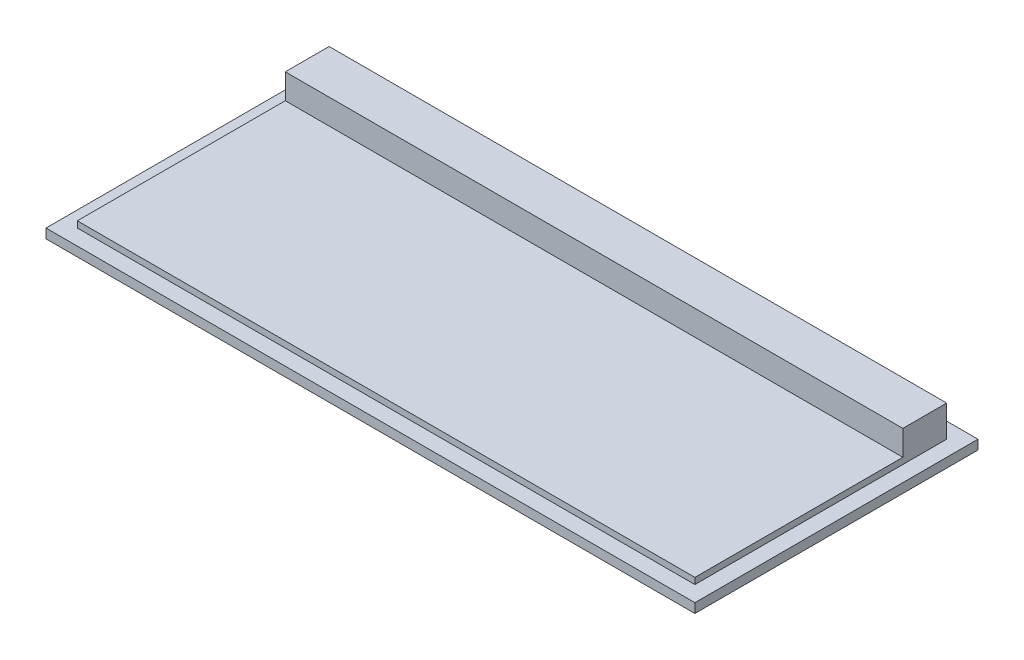
SolidWorks part; units mm, degrees
ref_plane "Front Plane" through (0, 0, 0) normal (0, 0, 1) x (1, 0, 0)
ref_plane "Top Plane" through (0, 0, 0) normal (0, 1, 0) x (1, 0, 0)
ref_plane "Right Plane" through (0, 0, 0) normal (1, 0, 0) x (0, 0, -1)
sketch "Sketch1" plane through (0, 0, 0) normal (1, 0, 0) x (0, 0, -1)
  line L0 (0, 0) -> (114.808, 0)
  line L28 (0, 0) -> (0, 3.81)
  line L29 (0, 3.81) -> (114.808, 3.81)
  line L30 (114.808, 0) -> (114.808, 3.81)
  dimension "D1" = 114.808
  dimension "D2" = 3.81
extrude "Boss-Extrude1" add sketch "Sketch1" along normal blind 263.144
sketch "Sketch2" plane through (0, 3.81, 0) normal (0, 1, 0) x (1, 0, 0)
  line L8 (6.35, 108.458) -> (6.35, 6.35)
  line L9 (6.35, 6.35) -> (256.794, 6.35)
  line L10 (256.794, 6.35) -> (256.794, 108.458)
  line L11 (256.794, 108.458) -> (6.35, 108.458)
  line L12 (6.35, 108.458) -> (6.35, 6.35)
  line L13 (6.35, 6.35) -> (256.794, 6.35)
  line L14 (256.794, 6.35) -> (256.794, 108.458)
  line L15 (256.794, 108.458) -> (6.35, 108.458)
  dimension "D1" = 6.35
extrude "Boss-Extrude2" add sketch "Sketch2" along normal blind 2.54
sketch "Sketch3" plane through (6.35, 0, 0) normal (-1, 0, 0) x (0, 0, 1)
  line L1 (-108.458, 6.35) -> (-90.678, 6.35)
  line L2 (-108.458, 6.35) -> (-108.458, 16.51)
  line L3 (-108.458, 16.51) -> (-90.678, 16.51)
  line L4 (-90.678, 6.35) -> (-90.678, 16.51)
  dimension "D1" = 10.16
  dimension "D2" = 17.78
extrude "Boss-Extrude3" add sketch "Sketch3" against normal blind 250.444
sketch "Sketch4" plane through (6.35, 0, 0) normal (-1, 0, 0) x (0, 0, 1)
  line L0 (-93.98, 7.112) -> (-93.98, 9.3148)
  line L2 (-105.156, 9.3148) -> (-105.156, 7.112)
  line L3 (-93.98, 7.112) -> (-105.156, 7.112)
  line L4 (-105.156, 9.3148) -> (-93.98, 9.3148)
  line L5 (-105.156, 13.208) -> (-105.156, 6.35) construction
  line L6 (-93.98, 6.35) -> (-93.98, 13.208) construction
  line L7 (-93.218, 6.35) -> (-105.918, 6.35)
  line L8 (-93.218, 7.112) -> (-105.918, 7.112) construction
  line L10 (-93.218, 6.35) -> (-93.218, 13.97)
  line L11 (-105.918, 13.97) -> (-105.918, 3.81)
  line L12 (-93.218, 13.97) -> (-105.918, 13.97)
  line L13 (-93.218, 6.35) -> (-93.218, 13.97)
  line L14 (-105.918, 13.97) -> (-105.918, 6.35)
  line L15 (-93.218, 13.97) -> (-105.918, 13.97)
  line L16 (-93.98, 13.208) -> (-105.156, 13.208) construction
  dimension "D4" = 2.2028
  dimension "D1" = 2.54
  dimension "D2" = 0.762
  dimension "D3" = 0.762
extrude "Cut-Extrude2" cut sketch "Sketch4" against normal blind 12.7
sketch "Sketch6" plane through (0, 9.3148, 0) normal (0, 1, 0) x (1, 0, 0)
  line L0 (7.8674, 100.4556) -> (7.8674, 99.0333)
  line L1 (7.8674, 103.2496) -> (17.4486, 103.2496)
  line L2 (7.8674, 103.2496) -> (7.8674, 101.8273)
  line L3 (7.8674, 101.8273) -> (17.4486, 101.8273)
  line L4 (17.4486, 103.2496) -> (17.4486, 101.8273)
  line L5 (7.8674, 100.4556) -> (17.4486, 100.4556)
  line L6 (17.4486, 100.4556) -> (17.4486, 99.0333)
  line L7 (7.8674, 99.0333) -> (17.4486, 99.0333)
  line L8 (7.8674, 97.6616) -> (7.8674, 96.2393)
  line L9 (7.8674, 97.6616) -> (17.4486, 97.6616)
  line L10 (17.4486, 97.6616) -> (17.4486, 96.2393)
  line L11 (7.8674, 96.2393) -> (17.4486, 96.2393)
  dimension "D1" = 9.5812
  dimension "D2" = 1.4222
  dimension "D3" = 101.8273
  dimension "D4" = 7.8674
  dimension "D5" = 3
extrude "Boss-Extrude4" add sketch "Sketch6" along normal blind 0.254
sketch "Sketch7" plane through (0, 0, 0) normal (0, -1, 0) x (1, 0, 0)
  line L72 (28.2706, -104.3102) -> (28.2706, -109.0361)
  line L88 (11.7606, -103.0402) -> (23.5018, -103.0402)
  line L114 (29.5406, -103.0402) -> (41.2818, -103.0402)
  line L115 (10.4906, -104.3102) -> (10.4906, -109.0361)
  line L116 (42.5518, -104.3102) -> (42.5518, -109.0361)
  line L117 (11.7606, -110.3061) -> (23.5018, -110.3061)
  line L118 (24.7718, -104.3102) -> (24.7718, -109.0361)
  line L119 (29.5406, -110.3061) -> (41.2818, -110.3061)
  line L120 (46.0506, -104.3102) -> (46.0506, -109.0361)
  line L121 (47.3206, -103.0402) -> (59.0618, -103.0402)
  line L122 (60.3318, -104.3102) -> (60.3318, -109.0361)
  line L123 (47.3206, -110.3061) -> (59.0618, -110.3061)
  line L124 (63.8306, -104.3102) -> (63.8306, -109.0361)
  line L125 (65.1006, -103.0402) -> (76.8418, -103.0402)
  line L126 (78.1118, -104.3102) -> (78.1118, -109.0361)
  line L127 (65.1006, -110.3061) -> (76.8418, -110.3061)
  line L128 (81.6106, -104.3102) -> (81.6106, -109.0361)
  line L129 (82.8806, -103.0402) -> (94.6218, -103.0402)
  line L130 (95.8918, -104.3102) -> (95.8918, -109.0361)
  line L131 (82.8806, -110.3061) -> (94.6218, -110.3061)
  line L132 (99.3906, -104.3102) -> (99.3906, -109.0361)
  line L133 (100.6606, -103.0402) -> (112.4018, -103.0402)
  line L134 (113.6718, -104.3102) -> (113.6718, -109.0361)
  line L135 (100.6606, -110.3061) -> (112.4018, -110.3061)
  line L136 (117.1706, -104.3102) -> (117.1706, -109.0361)
  line L137 (118.4406, -103.0402) -> (130.1818, -103.0402)
  line L138 (131.4518, -104.3102) -> (131.4518, -109.0361)
  line L139 (118.4406, -110.3061) -> (130.1818, -110.3061)
  line L140 (134.9506, -104.3102) -> (134.9506, -109.0361)
  line L141 (136.2206, -103.0402) -> (147.9618, -103.0402)
  line L142 (149.2318, -104.3102) -> (149.2318, -109.0361)
  line L143 (136.2206, -110.3061) -> (147.9618, -110.3061)
  line L144 (152.7306, -104.3102) -> (152.7306, -109.0361)
  line L145 (154.0006, -103.0402) -> (165.7418, -103.0402)
  line L146 (167.0118, -104.3102) -> (167.0118, -109.0361)
  line L147 (154.0006, -110.3061) -> (165.7418, -110.3061)
  line L148 (170.5106, -104.3102) -> (170.5106, -109.0361)
  line L149 (171.7806, -103.0402) -> (183.5218, -103.0402)
  line L150 (184.7918, -104.3102) -> (184.7918, -109.0361)
  line L151 (171.7806, -110.3061) -> (183.5218, -110.3061)
  line L152 (188.2906, -104.3102) -> (188.2906, -109.0361)
  line L153 (189.5606, -103.0402) -> (201.3018, -103.0402)
  line L154 (202.5718, -104.3102) -> (202.5718, -109.0361)
  line L155 (189.5606, -110.3061) -> (201.3018, -110.3061)
  line L156 (206.0706, -104.3102) -> (206.0706, -109.0361)
  line L157 (207.3406, -103.0402) -> (219.0818, -103.0402)
  line L158 (220.3518, -104.3102) -> (220.3518, -109.0361)
  line L159 (207.3406, -110.3061) -> (219.0818, -110.3061)
  line L160 (223.8506, -104.3102) -> (223.8506, -109.0361)
  line L161 (225.1206, -103.0402) -> (236.8618, -103.0402)
  line L162 (238.1318, -104.3102) -> (238.1318, -109.0361)
  line L163 (225.1206, -110.3061) -> (236.8618, -110.3061)
  line L164 (241.6306, -104.3102) -> (241.6306, -109.0361)
  line L165 (242.9006, -103.0402) -> (254.6418, -103.0402)
  line L166 (255.9118, -104.3102) -> (255.9118, -109.0361)
  line L167 (242.9006, -110.3061) -> (254.6418, -110.3061)
  line L168 (28.2086, -98.0792) -> (28.2086, -88.1833)
  line L169 (11.7606, -99.3492) -> (23.5018, -99.3492)
  line L170 (10.4906, -98.0792) -> (10.4906, -88.1833)
  line L171 (11.7606, -86.9133) -> (23.5018, -86.9133)
  line L172 (24.7718, -98.0792) -> (24.7718, -88.1833)
  line L173 (29.4786, -99.3492) -> (41.2197, -99.3492)
  line L174 (42.4897, -98.0792) -> (42.4897, -88.1833)
  line L175 (29.4786, -86.9133) -> (41.2197, -86.9133)
  line L176 (45.9265, -98.0792) -> (45.9265, -88.1833)
  line L177 (47.1965, -99.3492) -> (58.9376, -99.3492)
  line L178 (60.2076, -98.0792) -> (60.2076, -88.1833)
  line L179 (47.1965, -86.9133) -> (58.9376, -86.9133)
  line L180 (63.6444, -98.0792) -> (63.6444, -88.1833)
  line L181 (64.9144, -99.3492) -> (76.6555, -99.3492)
  line L182 (77.9255, -98.0792) -> (77.9255, -88.1833)
  line L183 (64.9144, -86.9133) -> (76.6555, -86.9133)
  line L184 (81.3623, -98.0792) -> (81.3623, -88.1833)
  line L185 (82.6323, -99.3492) -> (94.3734, -99.3492)
  line L186 (95.6434, -98.0792) -> (95.6434, -88.1833)
  line L187 (82.6323, -86.9133) -> (94.3734, -86.9133)
  line L188 (99.0802, -98.0792) -> (99.0802, -88.1833)
  line L189 (100.3502, -99.3492) -> (112.0914, -99.3492)
  line L190 (113.3614, -98.0792) -> (113.3614, -88.1833)
  line L191 (100.3502, -86.9133) -> (112.0914, -86.9133)
  line L192 (116.7981, -98.0792) -> (116.7981, -88.1833)
  line L193 (118.0681, -99.3492) -> (129.8093, -99.3492)
  line L194 (131.0793, -98.0792) -> (131.0793, -88.1833)
  line L195 (118.0681, -86.9133) -> (129.8093, -86.9133)
  line L196 (134.516, -98.0792) -> (134.516, -88.1833)
  line L197 (135.786, -99.3492) -> (147.5272, -99.3492)
  line L198 (148.7972, -98.0792) -> (148.7972, -88.1833)
  line L199 (135.786, -86.9133) -> (147.5272, -86.9133)
  line L200 (152.2339, -98.0792) -> (152.2339, -88.1833)
  line L201 (153.5039, -99.3492) -> (165.2451, -99.3492)
  line L202 (166.5151, -98.0792) -> (166.5151, -88.1833)
  line L203 (153.5039, -86.9133) -> (165.2451, -86.9133)
  line L204 (169.9519, -98.0792) -> (169.9519, -88.1833)
  line L205 (171.2219, -99.3492) -> (182.963, -99.3492)
  line L206 (184.233, -98.0792) -> (184.233, -88.1833)
  line L207 (171.2219, -86.9133) -> (182.963, -86.9133)
  line L208 (187.6698, -98.0792) -> (187.6698, -88.1833)
  line L209 (188.9398, -99.3492) -> (200.6809, -99.3492)
  line L210 (201.9509, -98.0792) -> (201.9509, -88.1833)
  line L211 (188.9398, -86.9133) -> (200.6809, -86.9133)
  line L212 (205.3877, -98.0792) -> (205.3877, -88.1833)
  line L213 (206.6577, -99.3492) -> (218.3988, -99.3492)
  line L214 (219.6688, -98.0792) -> (219.6688, -88.1833)
  line L215 (206.6577, -86.9133) -> (218.3988, -86.9133)
  line L216 (223.1056, -98.0792) -> (223.1056, -88.1833)
  line L217 (224.3756, -99.3492) -> (236.1167, -99.3492)
  line L218 (237.3867, -98.0792) -> (237.3867, -88.1833)
  line L219 (224.3756, -86.9133) -> (236.1167, -86.9133)
  line L220 (240.8235, -98.0792) -> (240.8235, -88.1833)
  line L221 (242.0935, -99.3492) -> (253.8347, -99.3492)
  line L222 (255.1047, -98.0792) -> (255.1047, -88.1833)
  line L223 (242.0935, -86.9133) -> (253.8347, -86.9133)
  line L224 (28.2086, -82.8392) -> (28.2086, -72.9433)
  line L225 (29.4786, -84.1092) -> (41.2197, -84.1092)
  line L226 (42.4897, -82.8392) -> (42.4897, -72.9433)
  line L227 (29.4786, -71.6733) -> (41.2197, -71.6733)
  line L228 (45.9265, -82.8392) -> (45.9265, -72.9433)
  line L229 (47.1965, -84.1092) -> (58.9376, -84.1092)
  line L230 (60.2076, -82.8392) -> (60.2076, -72.9433)
  line L231 (47.1965, -71.6733) -> (58.9376, -71.6733)
  line L232 (63.6444, -82.8392) -> (63.6444, -72.9433)
  line L233 (64.9144, -84.1092) -> (76.6555, -84.1092)
  line L234 (77.9255, -82.8392) -> (77.9255, -72.9433)
  line L235 (64.9144, -71.6733) -> (76.6555, -71.6733)
  line L236 (81.3623, -82.8392) -> (81.3623, -72.9433)
  line L237 (82.6323, -84.1092) -> (94.3734, -84.1092)
  line L238 (95.6434, -82.8392) -> (95.6434, -72.9433)
  line L239 (82.6323, -71.6733) -> (94.3734, -71.6733)
  line L240 (99.0802, -82.8392) -> (99.0802, -72.9433)
  line L241 (100.3502, -84.1092) -> (112.0914, -84.1092)
  line L242 (113.3614, -82.8392) -> (113.3614, -72.9433)
  line L243 (100.3502, -71.6733) -> (112.0914, -71.6733)
  line L244 (116.7981, -82.8392) -> (116.7981, -72.9433)
  line L245 (118.0681, -84.1092) -> (129.8093, -84.1092)
  line L246 (131.0793, -82.8392) -> (131.0793, -72.9433)
  line L247 (118.0681, -71.6733) -> (129.8093, -71.6733)
  line L248 (134.516, -82.8392) -> (134.516, -72.9433)
  line L249 (135.786, -84.1092) -> (147.5272, -84.1092)
  line L250 (148.7972, -82.8392) -> (148.7972, -72.9433)
  line L251 (135.786, -71.6733) -> (147.5272, -71.6733)
  line L252 (152.2339, -82.8392) -> (152.2339, -72.9433)
  line L253 (153.5039, -84.1092) -> (165.2451, -84.1092)
  line L254 (166.5151, -82.8392) -> (166.5151, -72.9433)
  line L255 (153.5039, -71.6733) -> (165.2451, -71.6733)
  line L256 (169.9519, -82.8392) -> (169.9519, -72.9433)
  line L257 (171.2219, -84.1092) -> (182.963, -84.1092)
  line L258 (184.233, -82.8392) -> (184.233, -72.9433)
  line L259 (171.2219, -71.6733) -> (182.963, -71.6733)
  line L260 (187.6698, -82.8392) -> (187.6698, -72.9433)
  line L261 (188.9398, -84.1092) -> (200.6809, -84.1092)
  line L262 (201.9509, -82.8392) -> (201.9509, -72.9433)
  line L263 (188.9398, -71.6733) -> (200.6809, -71.6733)
  line L264 (205.3877, -82.8392) -> (205.3877, -72.9433)
  line L265 (206.6577, -84.1092) -> (218.3988, -84.1092)
  line L266 (219.6688, -82.8392) -> (219.6688, -72.9433)
  line L267 (206.6577, -71.6733) -> (218.3988, -71.6733)
  line L268 (223.1056, -82.8392) -> (223.1056, -72.9433)
  line L269 (224.3756, -84.1092) -> (236.1167, -84.1092)
  line L270 (237.3867, -82.8392) -> (237.3867, -72.9433)
  line L271 (224.3756, -71.6733) -> (236.1167, -71.6733)
  line L272 (240.8235, -82.8392) -> (240.8235, -72.9433)
  line L273 (242.0935, -84.1092) -> (253.8347, -84.1092)
  line L274 (255.1047, -82.8392) -> (255.1047, -72.9433)
  line L275 (242.0935, -71.6733) -> (253.8347, -71.6733)
  line L276 (28.2086, -67.5992) -> (28.2086, -57.7033)
  line L277 (29.4786, -68.8692) -> (41.2197, -68.8692)
  line L278 (42.4897, -67.5992) -> (42.4897, -57.7033)
  line L279 (29.4786, -56.4333) -> (41.2197, -56.4333)
  line L280 (45.9265, -67.5992) -> (45.9265, -57.7033)
  line L281 (47.1965, -68.8692) -> (58.9376, -68.8692)
  line L282 (60.2076, -67.5992) -> (60.2076, -57.7033)
  line L283 (47.1965, -56.4333) -> (58.9376, -56.4333)
  line L284 (63.6444, -67.5992) -> (63.6444, -57.7033)
  line L285 (64.9144, -68.8692) -> (76.6555, -68.8692)
  line L286 (77.9255, -67.5992) -> (77.9255, -57.7033)
  line L287 (64.9144, -56.4333) -> (76.6555, -56.4333)
  line L288 (81.3623, -67.5992) -> (81.3623, -57.7033)
  line L289 (82.6323, -68.8692) -> (94.3734, -68.8692)
  line L290 (95.6434, -67.5992) -> (95.6434, -57.7033)
  line L291 (82.6323, -56.4333) -> (94.3734, -56.4333)
  line L292 (99.0802, -67.5992) -> (99.0802, -57.7033)
  line L293 (100.3502, -68.8692) -> (112.0914, -68.8692)
  line L294 (113.3614, -67.5992) -> (113.3614, -57.7033)
  line L295 (100.3502, -56.4333) -> (112.0914, -56.4333)
  line L296 (116.7981, -67.5992) -> (116.7981, -57.7033)
  line L297 (118.0681, -68.8692) -> (129.8093, -68.8692)
  line L298 (131.0793, -67.5992) -> (131.0793, -57.7033)
  line L299 (118.0681, -56.4333) -> (129.8093, -56.4333)
  line L300 (134.516, -67.5992) -> (134.516, -57.7033)
  line L301 (135.786, -68.8692) -> (147.5272, -68.8692)
  line L302 (148.7972, -67.5992) -> (148.7972, -57.7033)
  line L303 (135.786, -56.4333) -> (147.5272, -56.4333)
  line L304 (152.2339, -67.5992) -> (152.2339, -57.7033)
  line L305 (153.5039, -68.8692) -> (165.2451, -68.8692)
  line L306 (166.5151, -67.5992) -> (166.5151, -57.7033)
  line L307 (153.5039, -56.4333) -> (165.2451, -56.4333)
  line L308 (169.9519, -67.5992) -> (169.9519, -57.7033)
  line L309 (171.2219, -68.8692) -> (182.963, -68.8692)
  line L310 (184.233, -67.5992) -> (184.233, -57.7033)
  line L311 (171.2219, -56.4333) -> (182.963, -56.4333)
  line L312 (187.6698, -67.5992) -> (187.6698, -57.7033)
  line L313 (188.9398, -68.8692) -> (200.6809, -68.8692)
  line L314 (201.9509, -67.5992) -> (201.9509, -57.7033)
  line L315 (188.9398, -56.4333) -> (200.6809, -56.4333)
  line L316 (205.3877, -67.5992) -> (205.3877, -57.7033)
  line L317 (206.6577, -68.8692) -> (218.3988, -68.8692)
  line L318 (219.6688, -67.5992) -> (219.6688, -57.7033)
  line L319 (206.6577, -56.4333) -> (218.3988, -56.4333)
  line L320 (223.1056, -67.5992) -> (223.1056, -57.7033)
  line L321 (224.3756, -68.8692) -> (236.1167, -68.8692)
  line L322 (237.3867, -67.5992) -> (237.3867, -57.7033)
  line L323 (224.3756, -56.4333) -> (236.1167, -56.4333)
  line L324 (240.8235, -67.5992) -> (240.8235, -57.7033)
  line L325 (242.0935, -68.8692) -> (253.8347, -68.8692)
  line L326 (255.1047, -67.5992) -> (255.1047, -57.7033)
  line L327 (242.0935, -56.4333) -> (253.8347, -56.4333)
  line L328 (28.2086, -52.3592) -> (28.2086, -42.4633)
  line L329 (29.4786, -53.6292) -> (41.2197, -53.6292)
  line L330 (42.4897, -52.3592) -> (42.4897, -42.4633)
  line L331 (29.4786, -41.1933) -> (41.2197, -41.1933)
  line L332 (45.9265, -52.3592) -> (45.9265, -42.4633)
  line L333 (47.1965, -53.6292) -> (58.9376, -53.6292)
  line L334 (60.2076, -52.3592) -> (60.2076, -42.4633)
  line L335 (47.1965, -41.1933) -> (58.9376, -41.1933)
  line L336 (63.6444, -52.3592) -> (63.6444, -42.4633)
  line L337 (64.9144, -53.6292) -> (76.6555, -53.6292)
  line L338 (77.9255, -52.3592) -> (77.9255, -42.4633)
  line L339 (64.9144, -41.1933) -> (76.6555, -41.1933)
  line L340 (81.3623, -52.3592) -> (81.3623, -42.4633)
  line L341 (82.6323, -53.6292) -> (94.3734, -53.6292)
  line L342 (95.6434, -52.3592) -> (95.6434, -42.4633)
  line L343 (82.6323, -41.1933) -> (94.3734, -41.1933)
  line L344 (99.0802, -52.3592) -> (99.0802, -42.4633)
  line L345 (100.3502, -53.6292) -> (112.0914, -53.6292)
  line L346 (113.3614, -52.3592) -> (113.3614, -42.4633)
  line L347 (100.3502, -41.1933) -> (112.0914, -41.1933)
  line L348 (116.7981, -52.3592) -> (116.7981, -42.4633)
  line L349 (118.0681, -53.6292) -> (129.8093, -53.6292)
  line L350 (131.0793, -52.3592) -> (131.0793, -42.4633)
  line L351 (118.0681, -41.1933) -> (129.8093, -41.1933)
  line L352 (134.516, -52.3592) -> (134.516, -42.4633)
  line L353 (135.786, -53.6292) -> (147.5272, -53.6292)
  line L354 (148.7972, -52.3592) -> (148.7972, -42.4633)
  line L355 (135.786, -41.1933) -> (147.5272, -41.1933)
  line L356 (152.2339, -52.3592) -> (152.2339, -42.4633)
  line L357 (153.5039, -53.6292) -> (165.2451, -53.6292)
  line L358 (166.5151, -52.3592) -> (166.5151, -42.4633)
  line L359 (153.5039, -41.1933) -> (165.2451, -41.1933)
  line L360 (169.9519, -52.3592) -> (169.9519, -42.4633)
  line L361 (171.2219, -53.6292) -> (182.963, -53.6292)
  line L362 (184.233, -52.3592) -> (184.233, -42.4633)
  line L363 (171.2219, -41.1933) -> (182.963, -41.1933)
  line L364 (187.6698, -52.3592) -> (187.6698, -42.4633)
  line L365 (188.9398, -53.6292) -> (200.6809, -53.6292)
  line L366 (201.9509, -52.3592) -> (201.9509, -42.4633)
  line L367 (188.9398, -41.1933) -> (200.6809, -41.1933)
  line L368 (205.3877, -52.3592) -> (205.3877, -42.4633)
  line L369 (206.6577, -53.6292) -> (218.3988, -53.6292)
  line L370 (219.6688, -52.3592) -> (219.6688, -42.4633)
  line L371 (206.6577, -41.1933) -> (218.3988, -41.1933)
  line L372 (223.1056, -52.3592) -> (223.1056, -42.4633)
  line L373 (224.3756, -53.6292) -> (236.1167, -53.6292)
  line L374 (237.3867, -52.3592) -> (237.3867, -42.4633)
  line L375 (224.3756, -41.1933) -> (236.1167, -41.1933)
  line L376 (240.8235, -52.3592) -> (240.8235, -42.4633)
  line L377 (242.0935, -53.6292) -> (253.8347, -53.6292)
  line L378 (255.1047, -52.3592) -> (255.1047, -42.4633)
  line L379 (242.0935, -41.1933) -> (253.8347, -41.1933)
  line L380 (28.2086, -37.1192) -> (28.2086, -27.2233)
  line L381 (29.4786, -38.3892) -> (41.2197, -38.3892)
  line L382 (42.4897, -37.1192) -> (42.4897, -27.2233)
  line L383 (29.4786, -25.9533) -> (41.2197, -25.9533)
  line L384 (45.9265, -37.1192) -> (45.9265, -27.2233)
  line L385 (47.1965, -38.3892) -> (58.9376, -38.3892)
  line L386 (60.2076, -37.1192) -> (60.2076, -27.2233)
  line L387 (47.1965, -25.9533) -> (58.9376, -25.9533)
  line L388 (63.6444, -37.1192) -> (63.6444, -27.2233)
  line L389 (64.9144, -38.3892) -> (76.6555, -38.3892)
  line L390 (77.9255, -37.1192) -> (77.9255, -27.2233)
  line L391 (64.9144, -25.9533) -> (76.6555, -25.9533)
  line L392 (81.3623, -37.1192) -> (81.3623, -27.2233)
  line L393 (82.6323, -38.3892) -> (94.3734, -38.3892)
  line L394 (95.6434, -37.1192) -> (95.6434, -27.2233)
  line L395 (82.6323, -25.9533) -> (94.3734, -25.9533)
  line L396 (99.0802, -37.1192) -> (99.0802, -27.2233)
  line L397 (100.3502, -38.3892) -> (112.0914, -38.3892)
  line L398 (113.3614, -37.1192) -> (113.3614, -27.2233)
  line L399 (100.3502, -25.9533) -> (112.0914, -25.9533)
  line L400 (116.7981, -37.1192) -> (116.7981, -27.2233)
  line L401 (118.0681, -38.3892) -> (129.8093, -38.3892)
  line L402 (131.0793, -37.1192) -> (131.0793, -27.2233)
  line L403 (118.0681, -25.9533) -> (129.8093, -25.9533)
  line L404 (134.516, -37.1192) -> (134.516, -27.2233)
  line L405 (135.786, -38.3892) -> (147.5272, -38.3892)
  line L406 (148.7972, -37.1192) -> (148.7972, -27.2233)
  line L407 (135.786, -25.9533) -> (147.5272, -25.9533)
  line L408 (152.2339, -37.1192) -> (152.2339, -27.2233)
  line L409 (153.5039, -38.3892) -> (165.2451, -38.3892)
  line L410 (166.5151, -37.1192) -> (166.5151, -27.2233)
  line L411 (153.5039, -25.9533) -> (165.2451, -25.9533)
  line L412 (169.9519, -37.1192) -> (169.9519, -27.2233)
  line L413 (171.2219, -38.3892) -> (182.963, -38.3892)
  line L414 (184.233, -37.1192) -> (184.233, -27.2233)
  line L415 (171.2219, -25.9533) -> (182.963, -25.9533)
  line L416 (187.6698, -37.1192) -> (187.6698, -27.2233)
  line L417 (188.9398, -38.3892) -> (200.6809, -38.3892)
  line L418 (201.9509, -37.1192) -> (201.9509, -27.2233)
  line L419 (188.9398, -25.9533) -> (200.6809, -25.9533)
  line L420 (205.3877, -37.1192) -> (205.3877, -27.2233)
  line L421 (206.6577, -38.3892) -> (218.3988, -38.3892)
  line L422 (219.6688, -37.1192) -> (219.6688, -27.2233)
  line L423 (206.6577, -25.9533) -> (218.3988, -25.9533)
  line L424 (223.1056, -37.1192) -> (223.1056, -27.2233)
  line L425 (224.3756, -38.3892) -> (236.1167, -38.3892)
  line L426 (237.3867, -37.1192) -> (237.3867, -27.2233)
  line L427 (224.3756, -25.9533) -> (236.1167, -25.9533)
  line L428 (240.8235, -37.1192) -> (240.8235, -27.2233)
  line L429 (242.0935, -38.3892) -> (253.8347, -38.3892)
  line L430 (255.1047, -37.1192) -> (255.1047, -27.2233)
  line L431 (242.0935, -25.9533) -> (253.8347, -25.9533)
  line L432 (10.4906, -82.8392) -> (10.4906, -72.9433)
  line L433 (11.7606, -84.1092) -> (23.5018, -84.1092)
  line L434 (24.7718, -82.8392) -> (24.7718, -72.9433)
  line L435 (11.7606, -71.6733) -> (23.5018, -71.6733)
  line L436 (10.4906, -67.5992) -> (10.4906, -57.7033)
  line L437 (11.7606, -68.8692) -> (23.5018, -68.8692)
  line L438 (24.7718, -67.5992) -> (24.7718, -57.7033)
  line L439 (11.7606, -56.4333) -> (23.5018, -56.4333)
  line L440 (10.4906, -52.3592) -> (10.4906, -42.4633)
  line L441 (11.7606, -53.6292) -> (23.5018, -53.6292)
  line L442 (24.7718, -52.3592) -> (24.7718, -42.4633)
  line L443 (11.7606, -41.1933) -> (23.5018, -41.1933)
  line L444 (10.4906, -37.1192) -> (10.4906, -27.2233)
  line L445 (11.7606, -38.3892) -> (23.5018, -38.3892)
  line L446 (24.7718, -37.1192) -> (24.7718, -27.2233)
  line L447 (11.7606, -25.9533) -> (23.5018, -25.9533)
  line L456 (63.3401, -22.3062) -> (63.3401, -11.9933)
  line L457 (64.6101, -10.7233) -> (75.9343, -10.7233)
  line L458 (77.5445, -22.5142) -> (77.7011, -11.7854)
  line L459 (64.1931, -23.1593) -> (75.9343, -23.1593)
  line L460 (81.1201, -22.3062) -> (81.1201, -11.9933)
  line L461 (82.3901, -10.7233) -> (93.7143, -10.7233)
  line L462 (95.4013, -22.3062) -> (95.4013, -11.5764)
  line L463 (81.9731, -23.1593) -> (93.7143, -23.1593)
  line L464 (77.6228, -17.1498) -> (63.3401, -17.1498) construction
  line L465 (188.1526, -21.3738) -> (188.1526, -11.4778)
  line L466 (100.1019, -22.6438) -> (182.963, -22.6438)
  line L467 (98.8319, -21.3738) -> (98.8319, -11.4778)
  line L468 (100.1019, -10.2078) -> (182.963, -10.2078)
  line L469 (184.233, -21.3738) -> (184.233, -11.4778)
  line L470 (189.4226, -22.6438) -> (201.1637, -22.6438)
  line L471 (202.4337, -21.3738) -> (202.4337, -11.4778)
  line L472 (189.4226, -10.2078) -> (201.1637, -10.2078)
  line L473 (205.9326, -21.3738) -> (205.9326, -11.4778)
  line L474 (207.2026, -10.2078) -> (218.9437, -10.2078)
  line L475 (220.2137, -21.3738) -> (220.2137, -11.4778)
  line L476 (207.2026, -22.6438) -> (218.9437, -22.6438)
  line L477 (223.7126, -21.3738) -> (223.7126, -11.4778)
  line L478 (224.9826, -10.2078) -> (236.7237, -10.2078)
  line L479 (237.9937, -21.3738) -> (237.9937, -11.4778)
  line L480 (224.9826, -22.6438) -> (236.7237, -22.6438)
  line L481 (241.4926, -21.3738) -> (241.4926, -11.4778)
  line L482 (242.7626, -10.2078) -> (254.5037, -10.2078)
  line L483 (255.7737, -21.3738) -> (255.7737, -11.4778)
  line L484 (242.7626, -22.6438) -> (254.5037, -22.6438)
  line L486 (58.9322, -10.7233) -> (47.1911, -10.7233)
  line L487 (60.2022, -11.9933) -> (60.2022, -15.8798)
  line L488 (58.9322, -17.1498) -> (47.1911, -17.1498)
  line L489 (45.9211, -11.9933) -> (45.9211, -15.8798)
  line L490 (41.7025, -10.7534) -> (29.9613, -10.7534)
  line L491 (42.9725, -12.0234) -> (42.9725, -15.9098)
  line L492 (41.7025, -17.1798) -> (29.9613, -17.1798)
  line L493 (28.6913, -12.0234) -> (28.6913, -15.9098)
  line L494 (23.6426, -10.6966) -> (11.9015, -10.6966)
  line L495 (24.9126, -11.9666) -> (24.9126, -15.853)
  line L496 (23.6426, -17.123) -> (11.9015, -17.123)
  line L497 (10.6315, -11.9666) -> (10.6315, -15.853)
  line L498 (41.7025, -17.1798) -> (29.9613, -17.1798)
  line L499 (42.9725, -18.4498) -> (42.9725, -22.3363)
  line L500 (41.7025, -23.6063) -> (29.9613, -23.6063)
  line L501 (28.6913, -18.4498) -> (28.6913, -22.3363)
  arc A0 (10.4906, -109.0361) -> (11.7606, -110.3061) centre (11.7606, -109.0361) ccw
  arc A1 (23.5018, -110.3061) -> (24.7718, -109.0361) centre (23.5018, -109.0361) ccw
  arc A2 (23.5018, -103.0402) -> (24.7718, -104.3102) centre (23.5018, -104.3102) cw
  arc A3 (11.7606, -103.0402) -> (10.4906, -104.3102) centre (11.7606, -104.3102) ccw
  arc A4 (29.5406, -103.0402) -> (28.2706, -104.3102) centre (29.5406, -104.3102) ccw
  arc A5 (28.2706, -109.0361) -> (29.5406, -110.3061) centre (29.5406, -109.0361) ccw
  arc A6 (41.2818, -103.0402) -> (42.5518, -104.3102) centre (41.2818, -104.3102) cw
  arc A7 (41.2818, -110.3061) -> (42.5518, -109.0361) centre (41.2818, -109.0361) ccw
  arc A8 (47.3206, -103.0402) -> (46.0506, -104.3102) centre (47.3206, -104.3102) ccw
  arc A9 (46.0506, -109.0361) -> (47.3206, -110.3061) centre (47.3206, -109.0361) ccw
  arc A10 (59.0618, -103.0402) -> (60.3318, -104.3102) centre (59.0618, -104.3102) cw
  arc A11 (59.0618, -110.3061) -> (60.3318, -109.0361) centre (59.0618, -109.0361) ccw
  arc A12 (65.1006, -103.0402) -> (63.8306, -104.3102) centre (65.1006, -104.3102) ccw
  arc A13 (63.8306, -109.0361) -> (65.1006, -110.3061) centre (65.1006, -109.0361) ccw
  arc A14 (76.8418, -103.0402) -> (78.1118, -104.3102) centre (76.8418, -104.3102) cw
  arc A15 (76.8418, -110.3061) -> (78.1118, -109.0361) centre (76.8418, -109.0361) ccw
  arc A16 (82.8806, -103.0402) -> (81.6106, -104.3102) centre (82.8806, -104.3102) ccw
  arc A17 (81.6106, -109.0361) -> (82.8806, -110.3061) centre (82.8806, -109.0361) ccw
  arc A18 (94.6218, -103.0402) -> (95.8918, -104.3102) centre (94.6218, -104.3102) cw
  arc A19 (94.6218, -110.3061) -> (95.8918, -109.0361) centre (94.6218, -109.0361) ccw
  arc A20 (100.6606, -103.0402) -> (99.3906, -104.3102) centre (100.6606, -104.3102) ccw
  arc A21 (99.3906, -109.0361) -> (100.6606, -110.3061) centre (100.6606, -109.0361) ccw
  arc A22 (112.4018, -103.0402) -> (113.6718, -104.3102) centre (112.4018, -104.3102) cw
  arc A23 (112.4018, -110.3061) -> (113.6718, -109.0361) centre (112.4018, -109.0361) ccw
  arc A24 (118.4406, -103.0402) -> (117.1706, -104.3102) centre (118.4406, -104.3102) ccw
  arc A25 (117.1706, -109.0361) -> (118.4406, -110.3061) centre (118.4406, -109.0361) ccw
  arc A26 (130.1818, -103.0402) -> (131.4518, -104.3102) centre (130.1818, -104.3102) cw
  arc A27 (130.1818, -110.3061) -> (131.4518, -109.0361) centre (130.1818, -109.0361) ccw
  arc A28 (136.2206, -103.0402) -> (134.9506, -104.3102) centre (136.2206, -104.3102) ccw
  arc A29 (134.9506, -109.0361) -> (136.2206, -110.3061) centre (136.2206, -109.0361) ccw
  arc A30 (147.9618, -103.0402) -> (149.2318, -104.3102) centre (147.9618, -104.3102) cw
  arc A31 (147.9618, -110.3061) -> (149.2318, -109.0361) centre (147.9618, -109.0361) ccw
  arc A32 (154.0006, -103.0402) -> (152.7306, -104.3102) centre (154.0006, -104.3102) ccw
  arc A33 (152.7306, -109.0361) -> (154.0006, -110.3061) centre (154.0006, -109.0361) ccw
  arc A34 (165.7418, -103.0402) -> (167.0118, -104.3102) centre (165.7418, -104.3102) cw
  arc A35 (165.7418, -110.3061) -> (167.0118, -109.0361) centre (165.7418, -109.0361) ccw
  arc A36 (171.7806, -103.0402) -> (170.5106, -104.3102) centre (171.7806, -104.3102) ccw
  arc A37 (170.5106, -109.0361) -> (171.7806, -110.3061) centre (171.7806, -109.0361) ccw
  arc A38 (183.5218, -103.0402) -> (184.7918, -104.3102) centre (183.5218, -104.3102) cw
  arc A39 (183.5218, -110.3061) -> (184.7918, -109.0361) centre (183.5218, -109.0361) ccw
  arc A40 (189.5606, -103.0402) -> (188.2906, -104.3102) centre (189.5606, -104.3102) ccw
  arc A41 (188.2906, -109.0361) -> (189.5606, -110.3061) centre (189.5606, -109.0361) ccw
  arc A42 (201.3018, -103.0402) -> (202.5718, -104.3102) centre (201.3018, -104.3102) cw
  arc A43 (201.3018, -110.3061) -> (202.5718, -109.0361) centre (201.3018, -109.0361) ccw
  arc A44 (207.3406, -103.0402) -> (206.0706, -104.3102) centre (207.3406, -104.3102) ccw
  arc A45 (206.0706, -109.0361) -> (207.3406, -110.3061) centre (207.3406, -109.0361) ccw
  arc A46 (219.0818, -103.0402) -> (220.3518, -104.3102) centre (219.0818, -104.3102) cw
  arc A47 (219.0818, -110.3061) -> (220.3518, -109.0361) centre (219.0818, -109.0361) ccw
  arc A48 (225.1206, -103.0402) -> (223.8506, -104.3102) centre (225.1206, -104.3102) ccw
  arc A49 (223.8506, -109.0361) -> (225.1206, -110.3061) centre (225.1206, -109.0361) ccw
  arc A50 (236.8618, -103.0402) -> (238.1318, -104.3102) centre (236.8618, -104.3102) cw
  arc A51 (236.8618, -110.3061) -> (238.1318, -109.0361) centre (236.8618, -109.0361) ccw
  arc A52 (242.9006, -103.0402) -> (241.6306, -104.3102) centre (242.9006, -104.3102) ccw
  arc A53 (241.6306, -109.0361) -> (242.9006, -110.3061) centre (242.9006, -109.0361) ccw
  arc A54 (254.6418, -103.0402) -> (255.9118, -104.3102) centre (254.6418, -104.3102) cw
  arc A55 (254.6418, -110.3061) -> (255.9118, -109.0361) centre (254.6418, -109.0361) ccw
  arc A56 (23.5018, -99.3492) -> (24.7718, -98.0792) centre (23.5018, -98.0792) ccw
  arc A57 (11.7606, -99.3492) -> (10.4906, -98.0792) centre (11.7606, -98.0792) cw
  arc A58 (10.4906, -88.1833) -> (11.7606, -86.9133) centre (11.7606, -88.1833) cw
  arc A59 (23.5018, -86.9133) -> (24.7718, -88.1833) centre (23.5018, -88.1833) cw
  arc A60 (28.2086, -88.1833) -> (29.4786, -86.9133) centre (29.4786, -88.1833) cw
  arc A61 (29.4786, -99.3492) -> (28.2086, -98.0792) centre (29.4786, -98.0792) cw
  arc A62 (41.2197, -99.3492) -> (42.4897, -98.0792) centre (41.2197, -98.0792) ccw
  arc A63 (41.2197, -86.9133) -> (42.4897, -88.1833) centre (41.2197, -88.1833) cw
  arc A64 (45.9265, -88.1833) -> (47.1965, -86.9133) centre (47.1965, -88.1833) cw
  arc A65 (47.1965, -99.3492) -> (45.9265, -98.0792) centre (47.1965, -98.0792) cw
  arc A66 (58.9376, -99.3492) -> (60.2076, -98.0792) centre (58.9376, -98.0792) ccw
  arc A67 (58.9376, -86.9133) -> (60.2076, -88.1833) centre (58.9376, -88.1833) cw
  arc A68 (63.6444, -88.1833) -> (64.9144, -86.9133) centre (64.9144, -88.1833) cw
  arc A69 (64.9144, -99.3492) -> (63.6444, -98.0792) centre (64.9144, -98.0792) cw
  arc A70 (76.6555, -99.3492) -> (77.9255, -98.0792) centre (76.6555, -98.0792) ccw
  arc A71 (76.6555, -86.9133) -> (77.9255, -88.1833) centre (76.6555, -88.1833) cw
  arc A72 (81.3623, -88.1833) -> (82.6323, -86.9133) centre (82.6323, -88.1833) cw
  arc A73 (82.6323, -99.3492) -> (81.3623, -98.0792) centre (82.6323, -98.0792) cw
  arc A74 (94.3734, -99.3492) -> (95.6434, -98.0792) centre (94.3734, -98.0792) ccw
  arc A75 (94.3734, -86.9133) -> (95.6434, -88.1833) centre (94.3734, -88.1833) cw
  arc A76 (99.0802, -88.1833) -> (100.3502, -86.9133) centre (100.3502, -88.1833) cw
  arc A77 (100.3502, -99.3492) -> (99.0802, -98.0792) centre (100.3502, -98.0792) cw
  arc A78 (112.0914, -99.3492) -> (113.3614, -98.0792) centre (112.0914, -98.0792) ccw
  arc A79 (112.0914, -86.9133) -> (113.3614, -88.1833) centre (112.0914, -88.1833) cw
  arc A80 (116.7981, -88.1833) -> (118.0681, -86.9133) centre (118.0681, -88.1833) cw
  arc A81 (118.0681, -99.3492) -> (116.7981, -98.0792) centre (118.0681, -98.0792) cw
  arc A82 (129.8093, -99.3492) -> (131.0793, -98.0792) centre (129.8093, -98.0792) ccw
  arc A83 (129.8093, -86.9133) -> (131.0793, -88.1833) centre (129.8093, -88.1833) cw
  arc A84 (134.516, -88.1833) -> (135.786, -86.9133) centre (135.786, -88.1833) cw
  arc A85 (135.786, -99.3492) -> (134.516, -98.0792) centre (135.786, -98.0792) cw
  arc A86 (147.5272, -99.3492) -> (148.7972, -98.0792) centre (147.5272, -98.0792) ccw
  arc A87 (147.5272, -86.9133) -> (148.7972, -88.1833) centre (147.5272, -88.1833) cw
  arc A88 (152.2339, -88.1833) -> (153.5039, -86.9133) centre (153.5039, -88.1833) cw
  arc A89 (153.5039, -99.3492) -> (152.2339, -98.0792) centre (153.5039, -98.0792) cw
  arc A90 (165.2451, -99.3492) -> (166.5151, -98.0792) centre (165.2451, -98.0792) ccw
  arc A91 (165.2451, -86.9133) -> (166.5151, -88.1833) centre (165.2451, -88.1833) cw
  arc A92 (169.9519, -88.1833) -> (171.2219, -86.9133) centre (171.2219, -88.1833) cw
  arc A93 (171.2219, -99.3492) -> (169.9519, -98.0792) centre (171.2219, -98.0792) cw
  arc A94 (182.963, -99.3492) -> (184.233, -98.0792) centre (182.963, -98.0792) ccw
  arc A95 (182.963, -86.9133) -> (184.233, -88.1833) centre (182.963, -88.1833) cw
  arc A96 (187.6698, -88.1833) -> (188.9398, -86.9133) centre (188.9398, -88.1833) cw
  arc A97 (188.9398, -99.3492) -> (187.6698, -98.0792) centre (188.9398, -98.0792) cw
  arc A98 (200.6809, -99.3492) -> (201.9509, -98.0792) centre (200.6809, -98.0792) ccw
  arc A99 (200.6809, -86.9133) -> (201.9509, -88.1833) centre (200.6809, -88.1833) cw
  arc A100 (205.3877, -88.1833) -> (206.6577, -86.9133) centre (206.6577, -88.1833) cw
  arc A101 (206.6577, -99.3492) -> (205.3877, -98.0792) centre (206.6577, -98.0792) cw
  arc A102 (218.3988, -99.3492) -> (219.6688, -98.0792) centre (218.3988, -98.0792) ccw
  arc A103 (218.3988, -86.9133) -> (219.6688, -88.1833) centre (218.3988, -88.1833) cw
  arc A104 (223.1056, -88.1833) -> (224.3756, -86.9133) centre (224.3756, -88.1833) cw
  arc A105 (224.3756, -99.3492) -> (223.1056, -98.0792) centre (224.3756, -98.0792) cw
  arc A106 (236.1167, -99.3492) -> (237.3867, -98.0792) centre (236.1167, -98.0792) ccw
  arc A107 (236.1167, -86.9133) -> (237.3867, -88.1833) centre (236.1167, -88.1833) cw
  arc A108 (240.8235, -88.1833) -> (242.0935, -86.9133) centre (242.0935, -88.1833) cw
  arc A109 (242.0935, -99.3492) -> (240.8235, -98.0792) centre (242.0935, -98.0792) cw
  arc A110 (253.8347, -99.3492) -> (255.1047, -98.0792) centre (253.8347, -98.0792) ccw
  arc A111 (253.8347, -86.9133) -> (255.1047, -88.1833) centre (253.8347, -88.1833) cw
  arc A112 (28.2086, -72.9433) -> (29.4786, -71.6733) centre (29.4786, -72.9433) cw
  arc A113 (29.4786, -84.1092) -> (28.2086, -82.8392) centre (29.4786, -82.8392) cw
  arc A114 (41.2197, -84.1092) -> (42.4897, -82.8392) centre (41.2197, -82.8392) ccw
  arc A115 (41.2197, -71.6733) -> (42.4897, -72.9433) centre (41.2197, -72.9433) cw
  arc A116 (45.9265, -72.9433) -> (47.1965, -71.6733) centre (47.1965, -72.9433) cw
  arc A117 (47.1965, -84.1092) -> (45.9265, -82.8392) centre (47.1965, -82.8392) cw
  arc A118 (58.9376, -84.1092) -> (60.2076, -82.8392) centre (58.9376, -82.8392) ccw
  arc A119 (58.9376, -71.6733) -> (60.2076, -72.9433) centre (58.9376, -72.9433) cw
  arc A120 (63.6444, -72.9433) -> (64.9144, -71.6733) centre (64.9144, -72.9433) cw
  arc A121 (64.9144, -84.1092) -> (63.6444, -82.8392) centre (64.9144, -82.8392) cw
  arc A122 (76.6555, -84.1092) -> (77.9255, -82.8392) centre (76.6555, -82.8392) ccw
  arc A123 (76.6555, -71.6733) -> (77.9255, -72.9433) centre (76.6555, -72.9433) cw
  arc A124 (81.3623, -72.9433) -> (82.6323, -71.6733) centre (82.6323, -72.9433) cw
  arc A125 (82.6323, -84.1092) -> (81.3623, -82.8392) centre (82.6323, -82.8392) cw
  arc A126 (94.3734, -84.1092) -> (95.6434, -82.8392) centre (94.3734, -82.8392) ccw
  arc A127 (94.3734, -71.6733) -> (95.6434, -72.9433) centre (94.3734, -72.9433) cw
  arc A128 (99.0802, -72.9433) -> (100.3502, -71.6733) centre (100.3502, -72.9433) cw
  arc A129 (100.3502, -84.1092) -> (99.0802, -82.8392) centre (100.3502, -82.8392) cw
  arc A130 (112.0914, -84.1092) -> (113.3614, -82.8392) centre (112.0914, -82.8392) ccw
  arc A131 (112.0914, -71.6733) -> (113.3614, -72.9433) centre (112.0914, -72.9433) cw
  arc A132 (116.7981, -72.9433) -> (118.0681, -71.6733) centre (118.0681, -72.9433) cw
  arc A133 (118.0681, -84.1092) -> (116.7981, -82.8392) centre (118.0681, -82.8392) cw
  arc A134 (129.8093, -84.1092) -> (131.0793, -82.8392) centre (129.8093, -82.8392) ccw
  arc A135 (129.8093, -71.6733) -> (131.0793, -72.9433) centre (129.8093, -72.9433) cw
  arc A136 (134.516, -72.9433) -> (135.786, -71.6733) centre (135.786, -72.9433) cw
  arc A137 (135.786, -84.1092) -> (134.516, -82.8392) centre (135.786, -82.8392) cw
  arc A138 (147.5272, -84.1092) -> (148.7972, -82.8392) centre (147.5272, -82.8392) ccw
  arc A139 (147.5272, -71.6733) -> (148.7972, -72.9433) centre (147.5272, -72.9433) cw
  arc A140 (152.2339, -72.9433) -> (153.5039, -71.6733) centre (153.5039, -72.9433) cw
  arc A141 (153.5039, -84.1092) -> (152.2339, -82.8392) centre (153.5039, -82.8392) cw
  arc A142 (165.2451, -84.1092) -> (166.5151, -82.8392) centre (165.2451, -82.8392) ccw
  arc A143 (165.2451, -71.6733) -> (166.5151, -72.9433) centre (165.2451, -72.9433) cw
  arc A144 (169.9519, -72.9433) -> (171.2219, -71.6733) centre (171.2219, -72.9433) cw
  arc A145 (171.2219, -84.1092) -> (169.9519, -82.8392) centre (171.2219, -82.8392) cw
  arc A146 (182.963, -84.1092) -> (184.233, -82.8392) centre (182.963, -82.8392) ccw
  arc A147 (182.963, -71.6733) -> (184.233, -72.9433) centre (182.963, -72.9433) cw
  arc A148 (187.6698, -72.9433) -> (188.9398, -71.6733) centre (188.9398, -72.9433) cw
  arc A149 (188.9398, -84.1092) -> (187.6698, -82.8392) centre (188.9398, -82.8392) cw
  arc A150 (200.6809, -84.1092) -> (201.9509, -82.8392) centre (200.6809, -82.8392) ccw
  arc A151 (200.6809, -71.6733) -> (201.9509, -72.9433) centre (200.6809, -72.9433) cw
  arc A152 (205.3877, -72.9433) -> (206.6577, -71.6733) centre (206.6577, -72.9433) cw
  arc A153 (206.6577, -84.1092) -> (205.3877, -82.8392) centre (206.6577, -82.8392) cw
  arc A154 (218.3988, -84.1092) -> (219.6688, -82.8392) centre (218.3988, -82.8392) ccw
  arc A155 (218.3988, -71.6733) -> (219.6688, -72.9433) centre (218.3988, -72.9433) cw
  arc A156 (223.1056, -72.9433) -> (224.3756, -71.6733) centre (224.3756, -72.9433) cw
  arc A157 (224.3756, -84.1092) -> (223.1056, -82.8392) centre (224.3756, -82.8392) cw
  arc A158 (236.1167, -84.1092) -> (237.3867, -82.8392) centre (236.1167, -82.8392) ccw
  arc A159 (236.1167, -71.6733) -> (237.3867, -72.9433) centre (236.1167, -72.9433) cw
  arc A160 (240.8235, -72.9433) -> (242.0935, -71.6733) centre (242.0935, -72.9433) cw
  arc A161 (242.0935, -84.1092) -> (240.8235, -82.8392) centre (242.0935, -82.8392) cw
  arc A162 (253.8347, -84.1092) -> (255.1047, -82.8392) centre (253.8347, -82.8392) ccw
  arc A163 (253.8347, -71.6733) -> (255.1047, -72.9433) centre (253.8347, -72.9433) cw
  arc A164 (28.2086, -57.7033) -> (29.4786, -56.4333) centre (29.4786, -57.7033) cw
  arc A165 (29.4786, -68.8692) -> (28.2086, -67.5992) centre (29.4786, -67.5992) cw
  arc A166 (41.2197, -68.8692) -> (42.4897, -67.5992) centre (41.2197, -67.5992) ccw
  arc A167 (41.2197, -56.4333) -> (42.4897, -57.7033) centre (41.2197, -57.7033) cw
  arc A168 (45.9265, -57.7033) -> (47.1965, -56.4333) centre (47.1965, -57.7033) cw
  arc A169 (47.1965, -68.8692) -> (45.9265, -67.5992) centre (47.1965, -67.5992) cw
  arc A170 (58.9376, -68.8692) -> (60.2076, -67.5992) centre (58.9376, -67.5992) ccw
  arc A171 (58.9376, -56.4333) -> (60.2076, -57.7033) centre (58.9376, -57.7033) cw
  arc A172 (63.6444, -57.7033) -> (64.9144, -56.4333) centre (64.9144, -57.7033) cw
  arc A173 (64.9144, -68.8692) -> (63.6444, -67.5992) centre (64.9144, -67.5992) cw
  arc A174 (76.6555, -68.8692) -> (77.9255, -67.5992) centre (76.6555, -67.5992) ccw
  arc A175 (76.6555, -56.4333) -> (77.9255, -57.7033) centre (76.6555, -57.7033) cw
  arc A176 (81.3623, -57.7033) -> (82.6323, -56.4333) centre (82.6323, -57.7033) cw
  arc A177 (82.6323, -68.8692) -> (81.3623, -67.5992) centre (82.6323, -67.5992) cw
  arc A178 (94.3734, -68.8692) -> (95.6434, -67.5992) centre (94.3734, -67.5992) ccw
  arc A179 (94.3734, -56.4333) -> (95.6434, -57.7033) centre (94.3734, -57.7033) cw
  arc A180 (99.0802, -57.7033) -> (100.3502, -56.4333) centre (100.3502, -57.7033) cw
  arc A181 (100.3502, -68.8692) -> (99.0802, -67.5992) centre (100.3502, -67.5992) cw
  arc A182 (112.0914, -68.8692) -> (113.3614, -67.5992) centre (112.0914, -67.5992) ccw
  arc A183 (112.0914, -56.4333) -> (113.3614, -57.7033) centre (112.0914, -57.7033) cw
  arc A184 (116.7981, -57.7033) -> (118.0681, -56.4333) centre (118.0681, -57.7033) cw
  arc A185 (118.0681, -68.8692) -> (116.7981, -67.5992) centre (118.0681, -67.5992) cw
  arc A186 (129.8093, -68.8692) -> (131.0793, -67.5992) centre (129.8093, -67.5992) ccw
  arc A187 (129.8093, -56.4333) -> (131.0793, -57.7033) centre (129.8093, -57.7033) cw
  arc A188 (134.516, -57.7033) -> (135.786, -56.4333) centre (135.786, -57.7033) cw
  arc A189 (135.786, -68.8692) -> (134.516, -67.5992) centre (135.786, -67.5992) cw
  arc A190 (147.5272, -68.8692) -> (148.7972, -67.5992) centre (147.5272, -67.5992) ccw
  arc A191 (147.5272, -56.4333) -> (148.7972, -57.7033) centre (147.5272, -57.7033) cw
  arc A192 (152.2339, -57.7033) -> (153.5039, -56.4333) centre (153.5039, -57.7033) cw
  arc A193 (153.5039, -68.8692) -> (152.2339, -67.5992) centre (153.5039, -67.5992) cw
  arc A194 (165.2451, -68.8692) -> (166.5151, -67.5992) centre (165.2451, -67.5992) ccw
  arc A195 (165.2451, -56.4333) -> (166.5151, -57.7033) centre (165.2451, -57.7033) cw
  arc A196 (169.9519, -57.7033) -> (171.2219, -56.4333) centre (171.2219, -57.7033) cw
  arc A197 (171.2219, -68.8692) -> (169.9519, -67.5992) centre (171.2219, -67.5992) cw
  arc A198 (182.963, -68.8692) -> (184.233, -67.5992) centre (182.963, -67.5992) ccw
  arc A199 (182.963, -56.4333) -> (184.233, -57.7033) centre (182.963, -57.7033) cw
  arc A200 (187.6698, -57.7033) -> (188.9398, -56.4333) centre (188.9398, -57.7033) cw
  arc A201 (188.9398, -68.8692) -> (187.6698, -67.5992) centre (188.9398, -67.5992) cw
  arc A202 (200.6809, -68.8692) -> (201.9509, -67.5992) centre (200.6809, -67.5992) ccw
  arc A203 (200.6809, -56.4333) -> (201.9509, -57.7033) centre (200.6809, -57.7033) cw
  arc A204 (205.3877, -57.7033) -> (206.6577, -56.4333) centre (206.6577, -57.7033) cw
  arc A205 (206.6577, -68.8692) -> (205.3877, -67.5992) centre (206.6577, -67.5992) cw
  arc A206 (218.3988, -68.8692) -> (219.6688, -67.5992) centre (218.3988, -67.5992) ccw
  arc A207 (218.3988, -56.4333) -> (219.6688, -57.7033) centre (218.3988, -57.7033) cw
  arc A208 (223.1056, -57.7033) -> (224.3756, -56.4333) centre (224.3756, -57.7033) cw
  arc A209 (224.3756, -68.8692) -> (223.1056, -67.5992) centre (224.3756, -67.5992) cw
  arc A210 (236.1167, -68.8692) -> (237.3867, -67.5992) centre (236.1167, -67.5992) ccw
  arc A211 (236.1167, -56.4333) -> (237.3867, -57.7033) centre (236.1167, -57.7033) cw
  arc A212 (240.8235, -57.7033) -> (242.0935, -56.4333) centre (242.0935, -57.7033) cw
  arc A213 (242.0935, -68.8692) -> (240.8235, -67.5992) centre (242.0935, -67.5992) cw
  arc A214 (253.8347, -68.8692) -> (255.1047, -67.5992) centre (253.8347, -67.5992) ccw
  arc A215 (253.8347, -56.4333) -> (255.1047, -57.7033) centre (253.8347, -57.7033) cw
  arc A216 (28.2086, -42.4633) -> (29.4786, -41.1933) centre (29.4786, -42.4633) cw
  arc A217 (29.4786, -53.6292) -> (28.2086, -52.3592) centre (29.4786, -52.3592) cw
  arc A218 (41.2197, -53.6292) -> (42.4897, -52.3592) centre (41.2197, -52.3592) ccw
  arc A219 (41.2197, -41.1933) -> (42.4897, -42.4633) centre (41.2197, -42.4633) cw
  arc A220 (45.9265, -42.4633) -> (47.1965, -41.1933) centre (47.1965, -42.4633) cw
  arc A221 (47.1965, -53.6292) -> (45.9265, -52.3592) centre (47.1965, -52.3592) cw
  arc A222 (58.9376, -53.6292) -> (60.2076, -52.3592) centre (58.9376, -52.3592) ccw
  arc A223 (58.9376, -41.1933) -> (60.2076, -42.4633) centre (58.9376, -42.4633) cw
  arc A224 (63.6444, -42.4633) -> (64.9144, -41.1933) centre (64.9144, -42.4633) cw
  arc A225 (64.9144, -53.6292) -> (63.6444, -52.3592) centre (64.9144, -52.3592) cw
  arc A226 (76.6555, -53.6292) -> (77.9255, -52.3592) centre (76.6555, -52.3592) ccw
  arc A227 (76.6555, -41.1933) -> (77.9255, -42.4633) centre (76.6555, -42.4633) cw
  arc A228 (81.3623, -42.4633) -> (82.6323, -41.1933) centre (82.6323, -42.4633) cw
  arc A229 (82.6323, -53.6292) -> (81.3623, -52.3592) centre (82.6323, -52.3592) cw
  arc A230 (94.3734, -53.6292) -> (95.6434, -52.3592) centre (94.3734, -52.3592) ccw
  arc A231 (94.3734, -41.1933) -> (95.6434, -42.4633) centre (94.3734, -42.4633) cw
  arc A232 (99.0802, -42.4633) -> (100.3502, -41.1933) centre (100.3502, -42.4633) cw
  arc A233 (100.3502, -53.6292) -> (99.0802, -52.3592) centre (100.3502, -52.3592) cw
  arc A234 (112.0914, -53.6292) -> (113.3614, -52.3592) centre (112.0914, -52.3592) ccw
  arc A235 (112.0914, -41.1933) -> (113.3614, -42.4633) centre (112.0914, -42.4633) cw
  arc A236 (116.7981, -42.4633) -> (118.0681, -41.1933) centre (118.0681, -42.4633) cw
  arc A237 (118.0681, -53.6292) -> (116.7981, -52.3592) centre (118.0681, -52.3592) cw
  arc A238 (129.8093, -53.6292) -> (131.0793, -52.3592) centre (129.8093, -52.3592) ccw
  arc A239 (129.8093, -41.1933) -> (131.0793, -42.4633) centre (129.8093, -42.4633) cw
  arc A240 (134.516, -42.4633) -> (135.786, -41.1933) centre (135.786, -42.4633) cw
  arc A241 (135.786, -53.6292) -> (134.516, -52.3592) centre (135.786, -52.3592) cw
  arc A242 (147.5272, -53.6292) -> (148.7972, -52.3592) centre (147.5272, -52.3592) ccw
  arc A243 (147.5272, -41.1933) -> (148.7972, -42.4633) centre (147.5272, -42.4633) cw
  arc A244 (152.2339, -42.4633) -> (153.5039, -41.1933) centre (153.5039, -42.4633) cw
  arc A245 (153.5039, -53.6292) -> (152.2339, -52.3592) centre (153.5039, -52.3592) cw
  arc A246 (165.2451, -53.6292) -> (166.5151, -52.3592) centre (165.2451, -52.3592) ccw
  arc A247 (165.2451, -41.1933) -> (166.5151, -42.4633) centre (165.2451, -42.4633) cw
  arc A248 (169.9519, -42.4633) -> (171.2219, -41.1933) centre (171.2219, -42.4633) cw
  arc A249 (171.2219, -53.6292) -> (169.9519, -52.3592) centre (171.2219, -52.3592) cw
  arc A250 (182.963, -53.6292) -> (184.233, -52.3592) centre (182.963, -52.3592) ccw
  arc A251 (182.963, -41.1933) -> (184.233, -42.4633) centre (182.963, -42.4633) cw
  arc A252 (187.6698, -42.4633) -> (188.9398, -41.1933) centre (188.9398, -42.4633) cw
  arc A253 (188.9398, -53.6292) -> (187.6698, -52.3592) centre (188.9398, -52.3592) cw
  arc A254 (200.6809, -53.6292) -> (201.9509, -52.3592) centre (200.6809, -52.3592) ccw
  arc A255 (200.6809, -41.1933) -> (201.9509, -42.4633) centre (200.6809, -42.4633) cw
  arc A256 (205.3877, -42.4633) -> (206.6577, -41.1933) centre (206.6577, -42.4633) cw
  arc A257 (206.6577, -53.6292) -> (205.3877, -52.3592) centre (206.6577, -52.3592) cw
  arc A258 (218.3988, -53.6292) -> (219.6688, -52.3592) centre (218.3988, -52.3592) ccw
  arc A259 (218.3988, -41.1933) -> (219.6688, -42.4633) centre (218.3988, -42.4633) cw
  arc A260 (223.1056, -42.4633) -> (224.3756, -41.1933) centre (224.3756, -42.4633) cw
  arc A261 (224.3756, -53.6292) -> (223.1056, -52.3592) centre (224.3756, -52.3592) cw
  arc A262 (236.1167, -53.6292) -> (237.3867, -52.3592) centre (236.1167, -52.3592) ccw
  arc A263 (236.1167, -41.1933) -> (237.3867, -42.4633) centre (236.1167, -42.4633) cw
  arc A264 (240.8235, -42.4633) -> (242.0935, -41.1933) centre (242.0935, -42.4633) cw
  arc A265 (242.0935, -53.6292) -> (240.8235, -52.3592) centre (242.0935, -52.3592) cw
  arc A266 (253.8347, -53.6292) -> (255.1047, -52.3592) centre (253.8347, -52.3592) ccw
  arc A267 (253.8347, -41.1933) -> (255.1047, -42.4633) centre (253.8347, -42.4633) cw
  arc A268 (28.2086, -27.2233) -> (29.4786, -25.9533) centre (29.4786, -27.2233) cw
  arc A269 (29.4786, -38.3892) -> (28.2086, -37.1192) centre (29.4786, -37.1192) cw
  arc A270 (41.2197, -38.3892) -> (42.4897, -37.1192) centre (41.2197, -37.1192) ccw
  arc A271 (41.2197, -25.9533) -> (42.4897, -27.2233) centre (41.2197, -27.2233) cw
  arc A272 (45.9265, -27.2233) -> (47.1965, -25.9533) centre (47.1965, -27.2233) cw
  arc A273 (47.1965, -38.3892) -> (45.9265, -37.1192) centre (47.1965, -37.1192) cw
  arc A274 (58.9376, -38.3892) -> (60.2076, -37.1192) centre (58.9376, -37.1192) ccw
  arc A275 (58.9376, -25.9533) -> (60.2076, -27.2233) centre (58.9376, -27.2233) cw
  arc A276 (63.6444, -27.2233) -> (64.9144, -25.9533) centre (64.9144, -27.2233) cw
  arc A277 (64.9144, -38.3892) -> (63.6444, -37.1192) centre (64.9144, -37.1192) cw
  arc A278 (76.6555, -38.3892) -> (77.9255, -37.1192) centre (76.6555, -37.1192) ccw
  arc A279 (76.6555, -25.9533) -> (77.9255, -27.2233) centre (76.6555, -27.2233) cw
  arc A280 (81.3623, -27.2233) -> (82.6323, -25.9533) centre (82.6323, -27.2233) cw
  arc A281 (82.6323, -38.3892) -> (81.3623, -37.1192) centre (82.6323, -37.1192) cw
  arc A282 (94.3734, -38.3892) -> (95.6434, -37.1192) centre (94.3734, -37.1192) ccw
  arc A283 (94.3734, -25.9533) -> (95.6434, -27.2233) centre (94.3734, -27.2233) cw
  arc A284 (99.0802, -27.2233) -> (100.3502, -25.9533) centre (100.3502, -27.2233) cw
  arc A285 (100.3502, -38.3892) -> (99.0802, -37.1192) centre (100.3502, -37.1192) cw
  arc A286 (112.0914, -38.3892) -> (113.3614, -37.1192) centre (112.0914, -37.1192) ccw
  arc A287 (112.0914, -25.9533) -> (113.3614, -27.2233) centre (112.0914, -27.2233) cw
  arc A288 (116.7981, -27.2233) -> (118.0681, -25.9533) centre (118.0681, -27.2233) cw
  arc A289 (118.0681, -38.3892) -> (116.7981, -37.1192) centre (118.0681, -37.1192) cw
  arc A290 (129.8093, -38.3892) -> (131.0793, -37.1192) centre (129.8093, -37.1192) ccw
  arc A291 (129.8093, -25.9533) -> (131.0793, -27.2233) centre (129.8093, -27.2233) cw
  arc A292 (134.516, -27.2233) -> (135.786, -25.9533) centre (135.786, -27.2233) cw
  arc A293 (135.786, -38.3892) -> (134.516, -37.1192) centre (135.786, -37.1192) cw
  arc A294 (147.5272, -38.3892) -> (148.7972, -37.1192) centre (147.5272, -37.1192) ccw
  arc A295 (147.5272, -25.9533) -> (148.7972, -27.2233) centre (147.5272, -27.2233) cw
  arc A296 (152.2339, -27.2233) -> (153.5039, -25.9533) centre (153.5039, -27.2233) cw
  arc A297 (153.5039, -38.3892) -> (152.2339, -37.1192) centre (153.5039, -37.1192) cw
  arc A298 (165.2451, -38.3892) -> (166.5151, -37.1192) centre (165.2451, -37.1192) ccw
  arc A299 (165.2451, -25.9533) -> (166.5151, -27.2233) centre (165.2451, -27.2233) cw
  arc A300 (169.9519, -27.2233) -> (171.2219, -25.9533) centre (171.2219, -27.2233) cw
  arc A301 (171.2219, -38.3892) -> (169.9519, -37.1192) centre (171.2219, -37.1192) cw
  arc A302 (182.963, -38.3892) -> (184.233, -37.1192) centre (182.963, -37.1192) ccw
  arc A303 (182.963, -25.9533) -> (184.233, -27.2233) centre (182.963, -27.2233) cw
  arc A304 (187.6698, -27.2233) -> (188.9398, -25.9533) centre (188.9398, -27.2233) cw
  arc A305 (188.9398, -38.3892) -> (187.6698, -37.1192) centre (188.9398, -37.1192) cw
  arc A306 (200.6809, -38.3892) -> (201.9509, -37.1192) centre (200.6809, -37.1192) ccw
  arc A307 (200.6809, -25.9533) -> (201.9509, -27.2233) centre (200.6809, -27.2233) cw
  arc A308 (205.3877, -27.2233) -> (206.6577, -25.9533) centre (206.6577, -27.2233) cw
  arc A309 (206.6577, -38.3892) -> (205.3877, -37.1192) centre (206.6577, -37.1192) cw
  arc A310 (218.3988, -38.3892) -> (219.6688, -37.1192) centre (218.3988, -37.1192) ccw
  arc A311 (218.3988, -25.9533) -> (219.6688, -27.2233) centre (218.3988, -27.2233) cw
  arc A312 (223.1056, -27.2233) -> (224.3756, -25.9533) centre (224.3756, -27.2233) cw
  arc A313 (224.3756, -38.3892) -> (223.1056, -37.1192) centre (224.3756, -37.1192) cw
  arc A314 (236.1167, -38.3892) -> (237.3867, -37.1192) centre (236.1167, -37.1192) ccw
  arc A315 (236.1167, -25.9533) -> (237.3867, -27.2233) centre (236.1167, -27.2233) cw
  arc A316 (240.8235, -27.2233) -> (242.0935, -25.9533) centre (242.0935, -27.2233) cw
  arc A317 (242.0935, -38.3892) -> (240.8235, -37.1192) centre (242.0935, -37.1192) cw
  arc A318 (253.8347, -38.3892) -> (255.1047, -37.1192) centre (253.8347, -37.1192) ccw
  arc A319 (253.8347, -25.9533) -> (255.1047, -27.2233) centre (253.8347, -27.2233) cw
  arc A320 (10.4906, -72.9433) -> (11.7606, -71.6733) centre (11.7606, -72.9433) cw
  arc A321 (11.7606, -84.1092) -> (10.4906, -82.8392) centre (11.7606, -82.8392) cw
  arc A322 (23.5018, -84.1092) -> (24.7718, -82.8392) centre (23.5018, -82.8392) ccw
  arc A323 (23.5018, -71.6733) -> (24.7718, -72.9433) centre (23.5018, -72.9433) cw
  arc A324 (10.4906, -57.7033) -> (11.7606, -56.4333) centre (11.7606, -57.7033) cw
  arc A325 (11.7606, -68.8692) -> (10.4906, -67.5992) centre (11.7606, -67.5992) cw
  arc A326 (23.5018, -68.8692) -> (24.7718, -67.5992) centre (23.5018, -67.5992) ccw
  arc A327 (23.5018, -56.4333) -> (24.7718, -57.7033) centre (23.5018, -57.7033) cw
  arc A328 (10.4906, -42.4633) -> (11.7606, -41.1933) centre (11.7606, -42.4633) cw
  arc A329 (11.7606, -53.6292) -> (10.4906, -52.3592) centre (11.7606, -52.3592) cw
  arc A330 (23.5018, -53.6292) -> (24.7718, -52.3592) centre (23.5018, -52.3592) ccw
  arc A331 (23.5018, -41.1933) -> (24.7718, -42.4633) centre (23.5018, -42.4633) cw
  arc A332 (10.4906, -27.2233) -> (11.7606, -25.9533) centre (11.7606, -27.2233) cw
  arc A333 (11.7606, -38.3892) -> (10.4906, -37.1192) centre (11.7606, -37.1192) cw
  arc A334 (23.5018, -38.3892) -> (24.7718, -37.1192) centre (23.5018, -37.1192) ccw
  arc A335 (23.5018, -25.9533) -> (24.7718, -27.2233) centre (23.5018, -27.2233) cw
  arc A344 (63.3401, -11.9933) -> (64.6101, -10.7233) centre (64.6101, -11.9933) cw
  arc A345 (75.9343, -10.7233) -> (77.7011, -11.7854) centre (76.3792, -11.9838) cw
  arc A346 (75.9343, -23.1593) -> (77.5445, -22.5142) centre (76.3611, -21.8925) ccw
  arc A347 (64.1931, -23.1593) -> (63.3401, -22.3062) centre (64.6101, -21.8893) cw
  arc A348 (81.1201, -11.9933) -> (82.3901, -10.7233) centre (82.3901, -11.9933) cw
  arc A349 (93.7143, -10.7233) -> (95.4013, -11.5764) centre (94.1313, -11.9933) cw
  arc A350 (93.7143, -23.1593) -> (95.4013, -22.3062) centre (94.1313, -21.8893) ccw
  arc A351 (81.9731, -23.1593) -> (81.1201, -22.3062) centre (82.3901, -21.8893) cw
  arc A352 (188.1526, -11.4778) -> (189.4226, -10.2078) centre (189.4226, -11.4778) cw
  arc A353 (189.4226, -22.6438) -> (188.1526, -21.3738) centre (189.4226, -21.3738) cw
  arc A354 (201.1637, -22.6438) -> (202.4337, -21.3738) centre (201.1637, -21.3738) ccw
  arc A355 (201.1637, -10.2078) -> (202.4337, -11.4778) centre (201.1637, -11.4778) cw
  arc A356 (205.9326, -11.4778) -> (207.2026, -10.2078) centre (207.2026, -11.4778) cw
  arc A357 (218.9437, -10.2078) -> (220.2137, -11.4778) centre (218.9437, -11.4778) cw
  arc A358 (218.9437, -22.6438) -> (220.2137, -21.3738) centre (218.9437, -21.3738) ccw
  arc A359 (207.2026, -22.6438) -> (205.9326, -21.3738) centre (207.2026, -21.3738) cw
  arc A360 (223.7126, -11.4778) -> (224.9826, -10.2078) centre (224.9826, -11.4778) cw
  arc A361 (236.7237, -10.2078) -> (237.9937, -11.4778) centre (236.7237, -11.4778) cw
  arc A362 (236.7237, -22.6438) -> (237.9937, -21.3738) centre (236.7237, -21.3738) ccw
  arc A363 (224.9826, -22.6438) -> (223.7126, -21.3738) centre (224.9826, -21.3738) cw
  arc A364 (241.4926, -11.4778) -> (242.7626, -10.2078) centre (242.7626, -11.4778) cw
  arc A365 (254.5037, -10.2078) -> (255.7737, -11.4778) centre (254.5037, -11.4778) cw
  arc A366 (254.5037, -22.6438) -> (255.7737, -21.3738) centre (254.5037, -21.3738) ccw
  arc A367 (242.7626, -22.6438) -> (241.4926, -21.3738) centre (242.7626, -21.3738) cw
  arc A368 (98.8319, -11.4778) -> (100.1019, -10.2078) centre (100.1019, -11.4778) cw
  arc A369 (100.1019, -22.6438) -> (98.8319, -21.3738) centre (100.1019, -21.3738) cw
  arc A370 (182.963, -22.6438) -> (184.233, -21.3738) centre (182.963, -21.3738) ccw
  arc A371 (182.963, -10.2078) -> (184.233, -11.4778) centre (182.963, -11.4778) cw
  arc A372 (47.1911, -17.1498) -> (45.9211, -15.8798) centre (47.1911, -15.8798) cw
  arc A373 (60.2022, -15.8798) -> (58.9322, -17.1498) centre (58.9322, -15.8798) cw
  arc A374 (58.9322, -10.7233) -> (60.2022, -11.9933) centre (58.9322, -11.9933) cw
  arc A375 (47.1911, -10.7233) -> (45.9211, -11.9933) centre (47.1911, -11.9933) ccw
  arc A376 (29.9613, -17.1798) -> (28.6913, -15.9098) centre (29.9613, -15.9098) cw
  arc A377 (42.9725, -15.9098) -> (41.7025, -17.1798) centre (41.7025, -15.9098) cw
  arc A378 (41.7025, -10.7534) -> (42.9725, -12.0234) centre (41.7025, -12.0234) cw
  arc A379 (29.9613, -10.7534) -> (28.6913, -12.0234) centre (29.9613, -12.0234) ccw
  arc A380 (11.9015, -17.123) -> (10.6315, -15.853) centre (11.9015, -15.853) cw
  arc A381 (24.9126, -15.853) -> (23.6426, -17.123) centre (23.6426, -15.853) cw
  arc A382 (23.6426, -10.6966) -> (24.9126, -11.9666) centre (23.6426, -11.9666) cw
  arc A383 (11.9015, -10.6966) -> (10.6315, -11.9666) centre (11.9015, -11.9666) ccw
  arc A384 (29.9613, -23.6063) -> (28.6913, -22.3363) centre (29.9613, -22.3363) cw
  arc A385 (42.9725, -22.3363) -> (41.7025, -23.6063) centre (41.7025, -22.3363) cw
  arc A386 (41.7025, -17.1798) -> (42.9725, -18.4498) centre (41.7025, -18.4498) cw
  arc A387 (29.9613, -17.1798) -> (28.6913, -18.4498) centre (29.9613, -18.4498) ccw
  point P1020 (17.6312, -25.9533)
  point P1145 (0, 0)
  dimension "D1" = 1.27
  dimension "D3" = 1.27
  dimension "D8" = 1.27
  dimension "D6" = 1.27
  dimension "D2" = 14
  dimension "D4" = 14
  dimension "D5" = 5
extrude "Boss-Extrude5" add sketch "Sketch7" along normal blind 1.27 contours A331 L443 A328 L440 A329 L441 A330 L442 | A227 L339 A224 L336 A225 L337 A226 L338 | A231 L343 A228 L340 A229 L341 A230 L342 | A235 L347 A232 L344 A233 L345 A234 L346 | A239 L351 A236 L348 A237 L349 A238 L350 | A243 L355 A240 L352 A241 L353 A242 L354 | A295 L407 A292 L404 A293 L405 A294 L406 | A299 L411 A296 L408 A297 L409 A298 L410 | A247 L359 A244 L356 A245 L357 A246 L358 | A303 L415 A300 L412 A301 L413 A302 L414 | A251 L363 A248 L360 A249 L361 A250 L362 | A327 L439 A324 L436 A325 L437 A326 L438 | A167 L279 A164 L276 A165 L277 A166 L278 | A171 L283 A168 L280 A169 L281 A170 L282 | A175 L287 A172 L284 A173 L285 A174 L286 | A179 L291 A176 L288 A177 L289 A178 L290 | A183 L295 A180 L292 A181 L293 A182 L294 | A187 L299 A184 L296 A185 L297 A186 L298 | A323 L435 A320 L432 A321 L433 A322 L434 | A115 L227 A112 L224 A113 L225 A114 L226 | A119 L231 A116 L228 A117 L229 A118 L230 | A123 L235 A120 L232 A121 L233 A122 L234 | A127 L239 A124 L236 A125 L237 A126 L238 | A131 L243 A128 L240 A129 L241 A130 L242 | A135 L247 A132 L244 A133 L245 A134 L246 | A59 L171 A58 L170 A57 L169 A56 L172 | A63 L175 A60 L168 A61 L173 A62 L174 | A67 L179 A64 L176 A65 L177 A66 L178 | A71 L183 A68 L180 A69 L181 A70 L182 | A75 L187 A72 L184 A73 L185 A74 L186 | A79 L191 A76 L188 A77 L189 A78 L190 | L88 A3 L115 A0 L117 A1 L118 A2 | L119 A7 L116 A6 L114 A4 L72 A5 | L123 A11 L122 A10 L121 A8 L120 A9 | L127 A15 L126 A14 L125 A12 L124 A13 | L131 A19 L130 A18 L129 A16 L128 A17 | L135 A23 L134 A22 L133 A20 L132 A21 | L139 A27 L138 A26 L137 A24 L136 A25 | A83 L195 A80 L192 A81 L193 A82 L194 | A87 L199 A84 L196 A85 L197 A86 L198 | L143 A31 L142 A30 L141 A28 L140 A29 | L147 A35 L146 A34 L145 A32 L144 A33 | A91 L203 A88 L200 A89 L201 A90 L202 | A95 L207 A92 L204 A93 L205 A94 L206 | L151 A39 L150 A38 L149 A36 L148 A37 | L155 A43 L154 A42 L153 A40 L152 A41 | A99 L211 A96 L208 A97 L209 A98 L210 | A103 L215 A100 L212 A101 L213 A102 L214 | L159 A47 L158 A46 L157 A44 L156 A45 | L163 A51 L162 A50 L161 A48 L160 A49 | L167 A55 L166 A54 L165 A52 L164 A53 | A107 L219 A104 L216 A105 L217 A106 L218 | A111 L223 A108 L220 A109 L221 A110 L222 | A163 L275 A160 L272 A161 L273 A162 L274 | A159 L271 A156 L268 A157 L269 A158 L270 | A155 L267 A152 L264 A153 L265 A154 L266 | A151 L263 A148 L260 A149 L261 A150 L262 | A147 L259 A144 L256 A145 L257 A146 L258 | A143 L255 A140 L252 A141 L253 A142 L254 | A139 L251 A136 L248 A137 L249 A138 L250 | A191 L303 A188 L300 A189 L301 A190 L302 | A195 L307 A192 L304 A193 L305 A194 L306 | A199 L311 A196 L308 A197 L309 A198 L310 | A203 L315 A200 L312 A201 L313 A202 L314 | A207 L319 A204 L316 A205 L317 A206 L318 | A211 L323 A208 L320 A209 L321 A210 L322 | A215 L327 A212 L324 A213 L325 A214 L326 | A255 L367 A252 L364 A253 L365 A254 L366 | A259 L371 A256 L368 A257 L369 A258 L370 | A263 L375 A260 L372 A261 L373 A262 L374 | A267 L379 A264 L376 A265 L377 A266 L378 | A319 L431 A316 L428 A317 L429 A318 L430 | A315 L427 A312 L424 A313 L425 A314 L426 | A311 L423 A308 L420 A309 L421 A310 L422 | A307 L419 A304 L416 A305 L417 A306 L418 | A355 L472 A352 L465 A353 L470 A354 L471 | A359 L476 A358 L475 A357 L474 A356 L473 | A363 L480 A362 L479 A361 L478 A360 L477 | A367 L484 A366 L483 A365 L482 A364 L481 | L446 A335 L447 A332 L444 A333 L445 A334 | L328 A216 L331 A219 L330 A218 L329 A217 | L494 A383 L497 A380 L496 A381 L495 A382 | L490 A379 L493 A376 L492 A377 L491 A378 | L498 A387 L501 A384 L500 A385 L499 A386 | L487 A373 L488 A372 L489 A375 L486 A374 | L456 A344 L457 A345 L458 A346 L459 A347 | L467 A368 L468 A371 L469 A370 L466 A369 | L460 A348 L461 A349 L462 A350 L463 A351 | L380 A268 L383 A271 L382 A270 L381 A269 | L384 A272 L387 A275 L386 A274 L385 A273 | L388 A276 L391 A279 L390 A278 L389 A277 | L392 A280 L395 A283 L394 A282 L393 A281 | L396 A284 L399 A287 L398 A286 L397 A285 | L400 A288 L403 A291 L402 A290 L401 A289 | L332 A220 L335 A223 L334 A222 L333 A221 region at (35.4112, 0, -106.6732) region at (17.6312, 0, -106.6732) region at (53.1912, 0, -106.6732) region at (70.9712, 0, -106.6732) region at (88.7512, 0, -106.6732) region at (106.5312, 0, -106.6732) region at (124.3112, 0, -106.6732) region at (142.0912, 0, -106.6732) region at (159.8712, 0, -106.6732) region at (177.6512, 0, -106.6732) region at (195.4312, 0, -106.6732) region at (213.2112, 0, -106.6732) region at (230.9912, 0, -106.6732) region at (248.7712, 0, -106.6732) region at (35.3491, 0, -93.1312) region at (17.6312, 0, -93.1312) region at (53.067, 0, -93.1312) region at (70.785, 0, -93.1312) region at (88.5029, 0, -93.1312) region at (106.2208, 0, -93.1312) region at (123.9387, 0, -93.1312) region at (141.6566, 0, -93.1312) region at (159.3745, 0, -93.1312) region at (177.0924, 0, -93.1312) region at (194.8103, 0, -93.1312) region at (212.5283, 0, -93.1312) region at (230.2462, 0, -93.1312) region at (247.9641, 0, -93.1312) region at (35.3491, 0, -77.8912) region at (53.067, 0, -77.8912) region at (70.785, 0, -77.8912) region at (88.5029, 0, -77.8912) region at (106.2208, 0, -77.8912) region at (123.9387, 0, -77.8912) region at (141.6566, 0, -77.8912) region at (159.3745, 0, -77.8912) region at (177.0924, 0, -77.8912) region at (194.8103, 0, -77.8912) region at (212.5283, 0, -77.8912) region at (230.2462, 0, -77.8912) region at (247.9641, 0, -77.8912) region at (35.3491, 0, -62.6512) region at (53.067, 0, -62.6512) region at (70.785, 0, -62.6512) region at (88.5029, 0, -62.6512) region at (106.2208, 0, -62.6512) region at (123.9387, 0, -62.6512) region at (141.6566, 0, -62.6512) region at (159.3745, 0, -62.6512) region at (177.0924, 0, -62.6512) region at (194.8103, 0, -62.6512) region at (212.5283, 0, -62.6512) region at (230.2462, 0, -62.6512) region at (247.9641, 0, -62.6512) region at (70.785, 0, -47.4112) region at (88.5029, 0, -47.4112) region at (106.2208, 0, -47.4112) region at (123.9387, 0, -47.4112) region at (141.6566, 0, -47.4112) region at (159.3745, 0, -47.4112)
